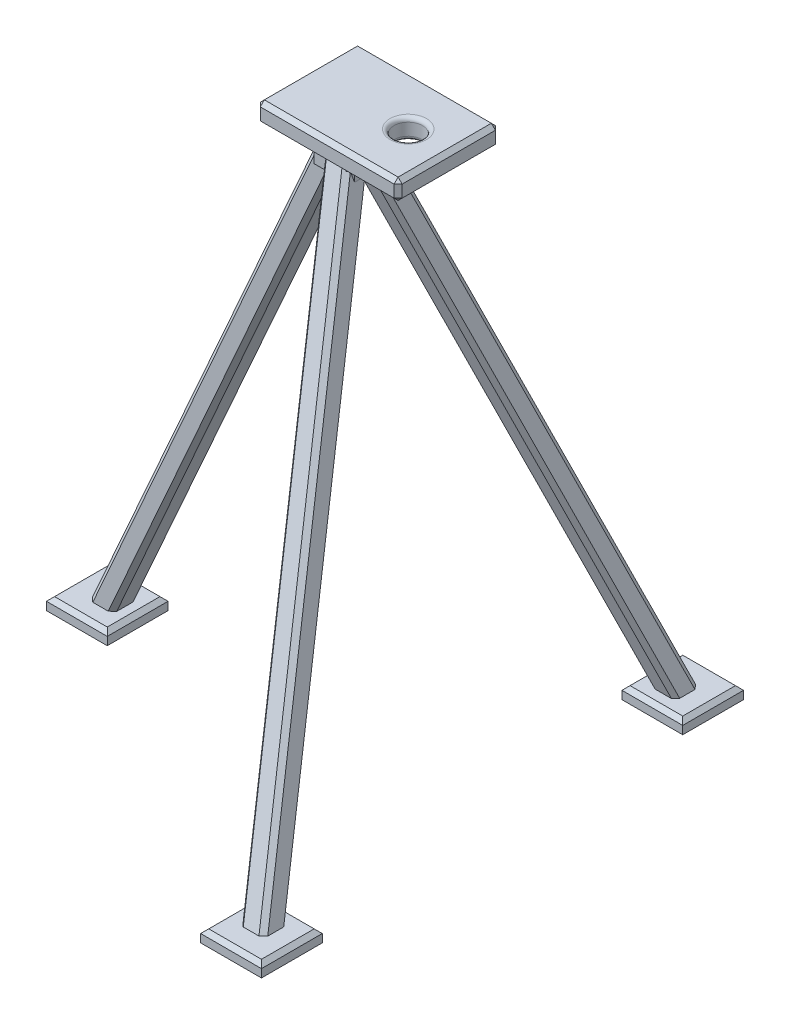
SolidWorks part; units mm, degrees
note: The reader was unsure of these and kept them because the rebuilt part matched: shared geometry of "Esboço5<4>", "Esboço5<5>".
ref_plane "Plano frontal" through (0, 0, 0) normal (0, 0, 1) x (1, 0, 0)
ref_plane "Plano superior" through (0, 0, 0) normal (0, 1, 0) x (1, 0, 0)
ref_plane "Plano direito" through (0, 0, 0) normal (1, 0, 0) x (0, 0, -1)
sketch "Esboço1" plane through (0, 0, 0) normal (0, 1, 0) x (1, 0, 0)
  line L1 (17.5, 12.5) -> (-17.5, 12.5)
  line L2 (17.5, 12.5) -> (17.5, -12.5)
  line L3 (17.5, -12.5) -> (-17.5, -12.5)
  line L4 (-17.5, 12.5) -> (-17.5, -12.5)
  line L5 (17.5, 12.5) -> (-17.5, -12.5) construction
  line L6 (17.5, -12.5) -> (-17.5, 12.5) construction
  circle A1 centre (7.5, 0) radius 3.5
  point P7 (0, 0)
  point P8 (0, 0)
  dimension "D1" = 7
  dimension "D2" = 25
  dimension "D3" = 35
  dimension "D4" = 10
  dimension "D5" = 0
extrude "Ressalto-extrusão1" add sketch "Esboço1" along normal blind 5
ref_plane "Plano1" through (0, -135, 0) normal (0, -1, 0) x (-1, 0, 0)
sketch "Esboço3" plane through (0, -135, 0) normal (0, -1, 0) x (-1, 0, 0)
  line L0 (-4, 0) -> (17.5, 0) construction
  line L1 (17.5, 12.5) -> (17.5, -12.5) construction
  line L2 (6.75, 0) -> (-23.25, -51.9615) construction
  line L4 (-23.25, 51.9615) -> (6.75, 0) construction
  line L5 (6.75, 0) -> (66.75, 0) construction
  circle A0 centre (-7.5, 0) radius 3.5 construction
  dimension "D1" = 120
  dimension "D2" = 120
  dimension "D3" = 60
  dimension "D4" = 60
  dimension "D5" = 60
sketch "Esboço4" plane through (0, -135, 0) normal (0, -1, 0) x (-1, 0, 0)
  line L1 (63.75, 3) -> (69.75, 3)
  line L2 (63.75, 3) -> (63.75, -3)
  line L3 (63.75, -3) -> (69.75, -3)
  line L4 (69.75, 3) -> (69.75, -3)
  line L5 (63.75, 3) -> (69.75, -3) construction
  line L6 (63.75, -3) -> (69.75, 3) construction
  point P0 (66.75, 0)
  dimension "D1" = 6
  dimension "D2" = 6
sketch "Esboço5" plane through (0, 0, 0) normal (0, -1, 0) x (1, 0, 0)
  line L0 (4, 0) -> (-17.5, 0) construction
  line L1 (-3.75, 3) -> (-9.75, 3)
  line L2 (-3.75, 3) -> (-3.75, -3)
  line L3 (-3.75, -3) -> (-9.75, -3)
  line L4 (-9.75, 3) -> (-9.75, -3)
  line L5 (-3.75, 3) -> (-9.75, -3) construction
  line L6 (-3.75, -3) -> (-9.75, 3) construction
  point P0 (-6.75, 0)
  dimension "D1" = 6
  dimension "D2" = 6
loft "Loft2" add profiles "Esboço5", "Esboço4"
sketch "Esboço6" plane through (0, -135, 0) normal (0, -1, 0) x (-1, 0, 0)
  line L1 (-26.25, 54.9615) -> (-20.25, 54.9615)
  line L2 (-26.25, 54.9615) -> (-26.25, 48.9615)
  line L3 (-26.25, 48.9615) -> (-20.25, 48.9615)
  line L4 (-20.25, 54.9615) -> (-20.25, 48.9615)
  line L5 (-26.25, 54.9615) -> (-20.25, 48.9615) construction
  line L6 (-26.25, 48.9615) -> (-20.25, 54.9615) construction
  point P0 (-23.25, 51.9615)
  dimension "D1" = 6
  dimension "D2" = 6
loft "Loft3" add profiles "Esboço6", "Esboço5<4>"
sketch "Esboço5<4>" plane through (0, 0, 0) normal (0, -1, 0) x (1, 0, 0) same geometry as "Esboço5"
sketch "Esboço7" plane through (0, -135, 0) normal (0, -1, 0) x (-1, 0, 0)
  line L1 (-26.25, -48.9615) -> (-20.25, -48.9615)
  line L2 (-26.25, -48.9615) -> (-26.25, -54.9615)
  line L3 (-26.25, -54.9615) -> (-20.25, -54.9615)
  line L4 (-20.25, -48.9615) -> (-20.25, -54.9615)
  line L5 (-26.25, -48.9615) -> (-20.25, -54.9615) construction
  line L6 (-26.25, -54.9615) -> (-20.25, -48.9615) construction
  point P0 (-23.25, -51.9615)
  dimension "D1" = 6
  dimension "D2" = 6
loft "Loft4" add profiles "Esboço7", "Esboço5<5>"
sketch "Esboço5<5>" plane through (0, 0, 0) normal (0, -1, 0) x (1, 0, 0) same geometry as "Esboço5"
ref_plane "Plano2" through (0, -10, 0) normal (0, -1, 0) x (-1, 0, 0)
sketch "Esboço8" plane through (0, -10, 0) normal (0, -1, 0) x (-1, 0, 0)
  line L16 (1.75, -5) -> (11.75, -5)
  line L17 (1.75, -5) -> (1.75, 5)
  line L18 (1.75, 5) -> (11.75, 5)
  line L19 (11.75, -5) -> (11.75, 5)
  line L20 (1.75, -5) -> (11.75, 5) construction
  line L21 (1.75, 5) -> (11.75, -5) construction
  point P0 (6.75, 0)
  dimension "D1" = 10
  dimension "D2" = 10
extrude "Ressalto-extrusão3" add sketch "Esboço8" against normal up to surface (10 mm away) up to face at (0, 0, 0)
sketch "Esboço9" plane through (0, -135, 0) normal (0, -1, 0) x (1, 0, 0)
  line L0 (26.25, -54.9615) -> (20.25, -48.9615) construction
  line L1 (-74.25, 7.5) -> (-59.25, 7.5)
  line L2 (-74.25, 7.5) -> (-74.25, -7.5)
  line L3 (-74.25, -7.5) -> (-59.25, -7.5)
  line L4 (-59.25, 7.5) -> (-59.25, -7.5)
  line L5 (-74.25, 7.5) -> (-59.25, -7.5) construction
  line L6 (-74.25, -7.5) -> (-59.25, 7.5) construction
  line L7 (15.75, 59.4615) -> (30.75, 59.4615)
  line L8 (15.75, 59.4615) -> (15.75, 44.4615)
  line L9 (15.75, 44.4615) -> (30.75, 44.4615)
  line L10 (30.75, 59.4615) -> (30.75, 44.4615)
  line L11 (15.75, 59.4615) -> (30.75, 44.4615) construction
  line L12 (15.75, 44.4615) -> (30.75, 59.4615) construction
  line L13 (15.75, -59.4615) -> (30.75, -59.4615)
  line L14 (15.75, -59.4615) -> (15.75, -44.4615)
  line L15 (15.75, -44.4615) -> (30.75, -44.4615)
  line L16 (30.75, -59.4615) -> (30.75, -44.4615)
  line L17 (15.75, -59.4615) -> (30.75, -44.4615) construction
  line L18 (15.75, -44.4615) -> (30.75, -59.4615) construction
  point P0 (-66.75, 0)
  point P6 (23.25, 51.9615)
  point P12 (23.25, -51.9615)
  dimension "D1" = 15
  dimension "D2" = 15
  dimension "D3" = 15
  dimension "D4" = 15
  dimension "D5" = 15
  dimension "D6" = 15
extrude "Ressalto-extrusão4" add sketch "Esboço9" against normal blind 3
chamfer "Chanfro2" distance 1 angle 45 14 edges at (-1.75, -9.5, -0.6566) (-1.75, -9.5, 0.6566)
chamfer "Chanfro3" distance 1 angle 45 9 edges at (-1.75, -10, -0.0204) (-1.75, -4.5, -5) (-11.75, -10, -4) (-9.6389, -10, -5) (-11.75, -5, -5) (-1.75, -4.5, 5) (-11.75, -10, 4) (-9.6389, -10, 5) (-11.75, -5, 5)
chamfer "Chanfro5" distance 1 angle 45 12 edges at (0, 5, 12.5) (0, 0, 12.5) (-17.5, 5, 0) (-17.5, 2.5, 12.5) (-17.5, 0, 0) (0, 5, -12.5) (-17.5, 2.5, -12.5) (0, 0, -12.5) (17.5, 2.5, 12.5) (17.5, 5, 0) (17.5, 2.5, -12.5) (17.5, 0, 0)
fillet "Filete1" radius 1 2 edges at (7.5, 0, 3.5) (7.5, 5, 3.5)
chamfer "Chanfro6" distance 1 angle 45 12 edges at (15.75, -132, -51.9615) (23.25, -132, -44.4615) (30.75, -132, -51.9615) (23.25, -132, -59.4615) (23.25, -132, 44.4615) (30.75, -132, 51.9615) (23.25, -132, 59.4615) (15.75, -132, 51.9615) (-74.25, -132, 0) (-66.75, -132, 7.5) (-59.25, -132, 0) (-66.75, -132, -7.5)
